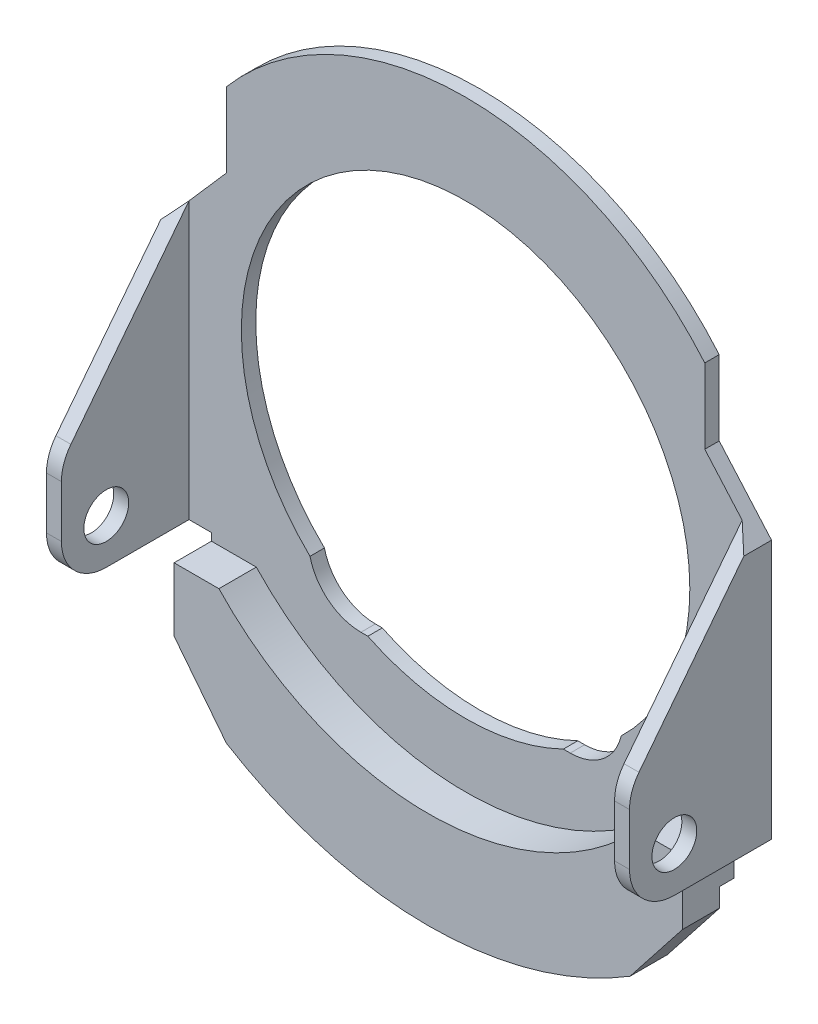
SolidWorks part; units mm, degrees
material "Alloy Steel"
ref_plane "Front Plane" through (0, 0, 0) normal (0, 0, 1) x (1, 0, 0)
ref_plane "Top Plane" through (0, 0, 0) normal (0, 1, 0) x (1, 0, 0)
ref_plane "Right Plane" through (0, 0, 0) normal (1, 0, 0) x (0, 0, -1)
sketch "Sketch1" plane through (0, 0, 0) normal (0, 0, 1) x (1, 0, 0)
  line L0 (-14, -27) -> (-13.0767, -27)
  line L1 (14, -27) -> (13.0767, -27)
  line L2 (0, 0) -> (0, 46.4413) construction
  line L3 (-32, 27.2029) -> (-32, 17.2029)
  line L4 (-32, 17.2029) -> (-39, 9.2029)
  line L5 (-39, 9.2029) -> (-39, -25.45)
  line L6 (39, 9.2029) -> (39, -25.45)
  line L7 (32, 17.2029) -> (39, 9.2029)
  line L8 (32, 27.2029) -> (32, 17.2029)
  line L9 (-34, -32.45) -> (-34, -25.45)
  line L10 (-34, -25.45) -> (-39, -25.45)
  line L11 (34, -25.45) -> (39, -25.45)
  line L12 (34, -32.45) -> (34, -25.45)
  line L13 (-37, 11.4887) -> (-37, -25.45)
  line L14 (37, 11.4887) -> (37, -25.45)
  line L25 (-27, -43.8549) -> (-34, -34.95)
  line L26 (-34, -34.95) -> (-34, -32.45)
  line L27 (34, -34.95) -> (34, -32.45)
  line L28 (27, -43.8549) -> (34, -34.95)
  line L29 (38.5, -34.2053) -> (38.5, -29.95) construction
  line L30 (38.5, -29.95) -> (43.5, -29.95) construction
  line L31 (43.5, 10.8937) -> (43.5, -29.95) construction
  line L32 (-43.5, 10.8937) -> (-43.5, -29.95) construction
  line L33 (-38.5, -29.95) -> (-43.5, -29.95) construction
  line L34 (-38.5, -34.2053) -> (-38.5, -29.95) construction
  line L35 (-36.5, 28.8097) -> (-36.5, 18.8937) construction
  line L36 (-36.5, 18.8937) -> (-43.5, 10.8937) construction
  line L37 (36.5, 28.8097) -> (36.5, 18.8937) construction
  line L38 (36.5, 18.8937) -> (43.5, 10.8937) construction
  line L39 (-34, -26.45) -> (-28, -26.45)
  line L40 (34, -26.45) -> (28, -26.45)
  arc A0 (-20.8134, -21.6056) -> (-14, -27) centre (-14, -20) ccw
  arc A1 (20.8134, -21.6056) -> (14, -27) centre (14, -20) cw
  arc A2 (20.8134, -21.6056) -> (-20.8134, -21.6056) centre (0, 0) ccw
  arc A3 (-13.0767, -27) -> (13.0767, -27) centre (0, 0) ccw
  arc A4 (32, 27.2029) -> (-32, 27.2029) centre (0, 0) ccw
  arc A5 (-34, -32.45) -> (34, -32.45) centre (0, 0) ccw
  arc A6 (-27, -43.8549) -> (27, -43.8549) centre (0, 0) ccw
  arc A8 (-38.5, -34.2053) -> (38.5, -34.2053) centre (0, 0) ccw construction
  arc A9 (36.5, 28.8097) -> (-36.5, 28.8097) centre (0, 0) ccw construction
  arc A10 (-28, -26.45) -> (28, -26.45) centre (0, 0) ccw
  dimension "D1" = 30
  dimension "D2" = 7
  dimension "D3" = 7
  dimension "D8" = 30
  dimension "D9" = 12
  dimension "D12" = 9
  dimension "D14" = 17
  dimension "D4" = 28
  dimension "D5" = 20
  dimension "D6" = 20
  dimension "D7" = 14
  dimension "D10" = 64
  dimension "D11" = 10
  dimension "D13" = 8
  dimension "D15" = 68
  dimension "D16" = 7
  dimension "D17" = 2
  dimension "D19" = 2.5
  dimension "D20" = 7
  dimension "D21" = 6
  dimension "D22" = 1
  dimension "D18" = 4.5
extrude "Boss-Extrude1" add sketch "Sketch1" along normal blind 1.93 contours L39 A10 L40 L12 L11 L14 L7 L8 A4 L3 L4 L13 L10 L9 A3 L0 A0 A2 A1 L1 | L13 L4 L5 L10 | L7 L14 L11 L6 | A10 L39 L9 A5 L12 L40 region at (0, 40.9064, 0) region at (-37.9894, -7.546, 0) region at (37.9894, -7.546, 0) region at (-31, -27.1603, 0)
extrude "Boss-Extrude2" add sketch "Sketch1<3>" along normal blind 5 from surface contours L25 A6 L28 L27 A5 L26 | A10 L39 L9 A5 L12 L40 region at (-31, -27.1603, 0) region at (0, -47.7062, 0) starting at face at (0, -17.496, 1.93)
sketch "Sketch1<3>" plane through (0, 0, 0) normal (0, 0, 1) x (1, 0, 0) same geometry as "Sketch1"
extrude "Boss-Extrude3" add sketch "Sketch1<4>" along normal blind 19 from surface contours L13 L4 L5 L10 | L7 L14 L11 L6 region at (-37.9894, -7.546, 0) region at (37.9894, -7.546, 0) starting at face at (0, -17.496, 0)
sketch "Sketch1<4>" plane through (0, 0, 0) normal (0, 0, 1) x (1, 0, 0) same geometry as "Sketch1"
sketch "Sketch3" plane through (0, 0, 0) normal (1, 0, 0) x (0, 0, -1)
  line L0 (-1.93, 11.4887) -> (-19, -10.45)
  line L5 (-1.93, -25.45) -> (-1.93, 11.4887) construction
  line L6 (-1.93, -25.45) -> (-1.93, 11.4887)
  line L7 (-19, 9.2029) -> (-19, -25.45) construction
  line L8 (-19, 11.4887) -> (-19, 9.2029) construction
  line L9 (-19, -25.45) -> (0, -25.45) construction
  line L10 (-19, 11.4887) -> (-1.93, 11.4887) construction
  line L11 (-19, 11.4887) -> (-19, 9.2029)
  line L12 (-19, 9.2029) -> (-19, -10.45)
  line L13 (-19, 11.4887) -> (-1.93, 11.4887)
  dimension "D1" = 15
extrude "Cut-Extrude1" cut sketch "Sketch3" against normal up to next and the other way up to next contours L13 L11 L12 L0
fillet "Fillet1" radius 6 4 edges at (38, -10.45, 19) (38, -25.45, 19) (-38, -25.45, 19) (-38, -10.45, 19)
sketch "Sketch5" plane through (0, 0, 0) normal (1, 0, 0) x (0, 0, -1)
  circle A0 centre (-13, -19.45) radius 3
  arc A1 (-19, -19.45) -> (-13, -25.45) centre (-13, -19.45) ccw construction
  dimension "D1" = 6
extrude "Cut-Extrude2" cut sketch "Sketch5" against normal up to next and the other way up to next
